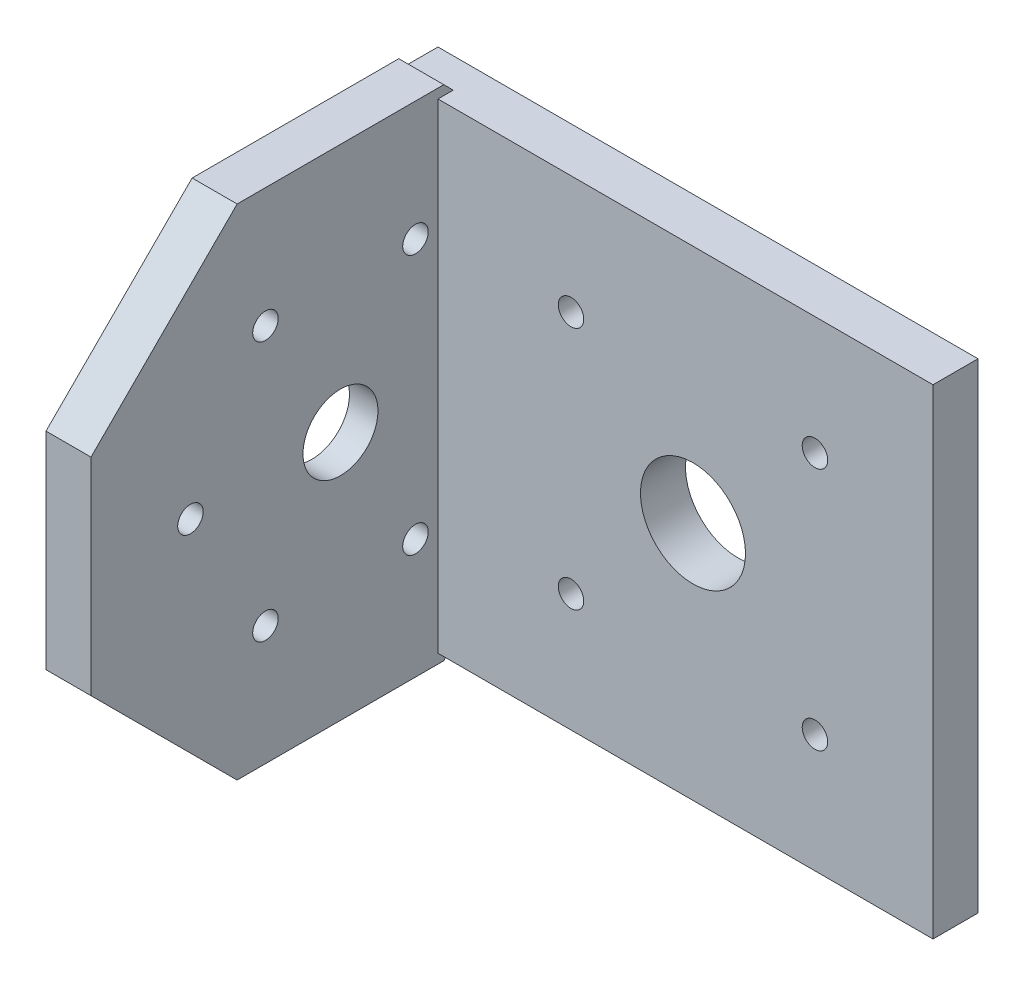
SolidWorks part; units mm, degrees
material "6061-T6 (SS)"
ref_plane "Front Plane" through (0, 0, 0) normal (0, 0, 1) x (1, 0, 0)
ref_plane "Top Plane" through (0, 0, 0) normal (0, 1, 0) x (1, 0, 0)
ref_plane "Right Plane" through (0, 0, 0) normal (1, 0, 0) x (0, 0, -1)
ref_plane "PL_Roll_Plate_base" through (-40, 0, 0) normal (1, 0, 0) x (0, 0, -1)
sketch "SK_Roll_Plate" plane through (-40, 0, 0) normal (1, 0, 0) x (0, 0, -1)
  line L0 (-13.7766, 33.2597) -> (-33.2597, 13.7766)
  line L1 (-33.2597, 13.7766) -> (-33.2597, -13.7766)
  line L2 (-33.2597, -13.7766) -> (-13.7766, -33.2597)
  line L3 (-13.7766, -33.2597) -> (13.7766, -33.2597)
  line L4 (13.7766, -33.2597) -> (33.2597, -13.7766)
  line L5 (33.2597, -13.7766) -> (33.2597, 13.7766)
  line L6 (33.2597, 13.7766) -> (13.7766, 33.2597)
  line L7 (13.7766, 33.2597) -> (-13.7766, 33.2597)
  circle A0 centre (20, 0) radius 1.7
  circle A1 centre (10, 17.3205) radius 1.7
  circle A2 centre (-10, 17.3205) radius 1.7
  circle A3 centre (-20, 0) radius 1.7
  circle A4 centre (-10, -17.3205) radius 1.7
  circle A5 centre (10, -17.3205) radius 1.7
  circle A6 centre (0, 0) radius 5
  dimension "D17_SK_Roll_Plate" = 3.4
  dimension "D19_SK_Roll_Plate" = 3.4
  dimension "D22_SK_Roll_Plate" = 3.4
  dimension "D25_SK_Roll_Plate" = 3.4
  dimension "D27_SK_Roll_Plate" = 3.4
  dimension "D30_SK_Roll_Plate" = 3.4
  dimension "D33_SK_Roll_Plate" = 10
  dimension "P1" = 13.7766
  dimension "P2" = 33.2597
  dimension "P3" = 33.2597
  dimension "P4" = 13.7766
  dimension "P5" = 33.2597
  dimension "P6" = 13.7766
  dimension "P7" = 13.7766
  dimension "P8" = 33.2597
  dimension "P9" = 13.7766
  dimension "P10" = 33.2597
  dimension "P11" = 33.2597
  dimension "P12" = 13.7766
  dimension "P13" = 33.2597
  dimension "P14" = 13.7766
  dimension "P15" = 13.7766
  dimension "P16" = 33.2597
  dimension "P18" = 20
  dimension "P20" = 10
  dimension "P21" = 17.3205
  dimension "P23" = 10
  dimension "P24" = 17.3205
  dimension "P26" = 20
  dimension "P28" = 10
  dimension "P29" = 17.3205
  dimension "P31" = 10
  dimension "P32" = 17.3205
extrude "Roll_Plate" add sketch "SK_Roll_Plate" along normal blind 6
ref_plane "PL_Yaw_Plate_base" through (0, 0, -19) normal (0, 0, 1) x (1, 0, 0)
sketch "SK_Yaw_Plate" plane through (0, 0, -19) normal (0, 0, 1) x (1, 0, 0)
  line L0 (-40, -32) -> (32, -32)
  line L1 (32, -32) -> (32, 32)
  line L2 (32, 32) -> (-40, 32)
  line L3 (-40, 32) -> (-40, -32)
  circle A0 centre (16.2635, 16.2635) radius 1.7
  circle A1 centre (-16.2635, 16.2635) radius 1.7
  circle A2 centre (-16.2635, -16.2635) radius 1.7
  circle A3 centre (16.2635, -16.2635) radius 1.7
  circle A4 centre (0, 0) radius 7
  dimension "D9_SK_Yaw_Plate" = 3.4
  dimension "D12_SK_Yaw_Plate" = 3.4
  dimension "D15_SK_Yaw_Plate" = 3.4
  dimension "D18_SK_Yaw_Plate" = 3.4
  dimension "D21_SK_Yaw_Plate" = 14
  dimension "P1" = 40
  dimension "P2" = 32
  dimension "P3" = 32
  dimension "P4" = 32
  dimension "P5" = 32
  dimension "P6" = 32
  dimension "P7" = 40
  dimension "P8" = 32
  dimension "P10" = 16.2635
  dimension "P11" = 16.2635
  dimension "P13" = 16.2635
  dimension "P14" = 16.2635
  dimension "P16" = 16.2635
  dimension "P17" = 16.2635
  dimension "P19" = 16.2635
  dimension "P20" = 16.2635
extrude "Yaw_Plate" add sketch "SK_Yaw_Plate" along normal blind 6
ref_plane "PL_Roll_Pilot_Recess_base" through (-40, 0, 0) normal (1, 0, 0) x (0, 0, -1)
sketch "SK_Roll_Pilot_Recess" plane through (-40, 0, 0) normal (1, 0, 0) x (0, 0, -1)
  circle A0 centre (0, 0) radius 15.15
  dimension "D1_SK_Roll_Pilot_Recess" = 30.3
extrude "Roll_Pilot_Recess" cut sketch "SK_Roll_Pilot_Recess" along normal blind 2.2
equation "\"Roll_face_x\"= -40"
equation "\"Yaw_rear_z\"= -19"
